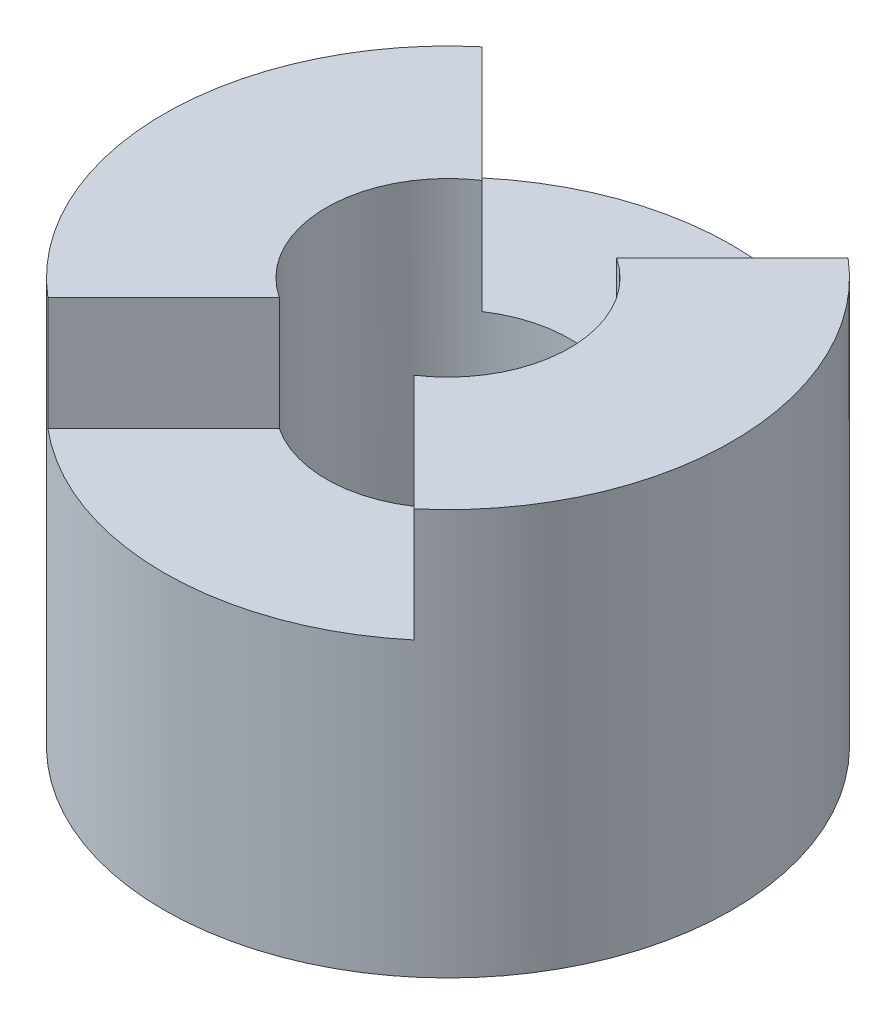
SolidWorks part; units mm, degrees
ref_plane "Front Plane" through (0, 0, 0) normal (0, 0, 1) x (1, 0, 0)
ref_plane "Top Plane" through (0, 0, 0) normal (0, 1, 0) x (1, 0, 0)
ref_plane "Right Plane" through (0, 0, 0) normal (1, 0, 0) x (0, 0, -1)
sketch "Sketch1" plane through (0, 0, 0) normal (0, 1, 0) x (1, 0, 0)
  circle A0 centre (0, 0) radius 35
  circle A1 centre (0, 0) radius 15
  dimension "D1" = 70
  dimension "D2" = 30
extrude "Boss-Extrude1" add sketch "Sketch1" along normal blind 50
sketch "Sketch2" plane through (0, 50, 0) normal (0, 1, 0) x (1, 0, 0)
  line L0 (0, 0) -> (45.0155, 0) construction
  line L1 (0, 0) -> (0, -60.2355) construction
  line L2 (8.2916, -12.5) -> (22.5549, -26.7633)
  line L3 (-8.2916, -12.5) -> (-22.5549, -26.7633)
  circle A0 centre (0, 0) radius 35 construction
  arc A1 (-22.5549, -26.7633) -> (22.5549, -26.7633) centre (0, 0) ccw
  circle A2 centre (0, 0) radius 15 construction
  arc A3 (-8.2916, -12.5) -> (8.2916, -12.5) centre (0, 0) ccw
extrude "Cut-Extrude1" cut sketch "Sketch2" against normal offset from surface (14 mm away) 36 up to face at (0, 0, 35)
ref_axis "Axis1" through (0, 50, 0) along (0, -1, 0)
mirror "Mirror1" about plane through (0, 0, 0) normal (0, 0, 1) of "Cut-Extrude1"
